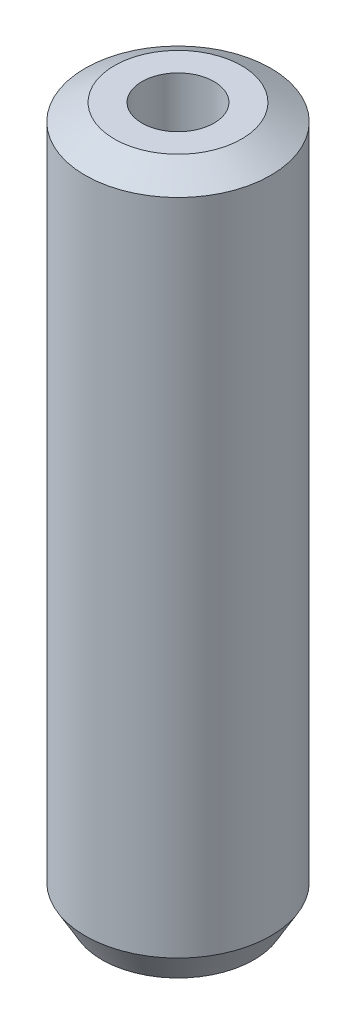
SolidWorks part; units mm, degrees
ref_plane "Front Plane" through (0, 0, 0) normal (0, 0, 1) x (1, 0, 0)
ref_plane "Top Plane" through (0, 0, 0) normal (0, 1, 0) x (1, 0, 0)
ref_plane "Right Plane" through (0, 0, 0) normal (1, 0, 0) x (0, 0, -1)
sketch "Sketch1" plane through (0, 0, 0) normal (0, 1, 0) x (1, 0, 0)
  circle A0 centre (0, 0) radius 22.5
  dimension "SHAFT_OD" = 45
extrude "Boss-Extrude1" add sketch "Sketch1" along normal blind 170.8514
sketch "Sketch2" plane through (0, 0, 0) normal (0, 1, 0) x (1, 0, 0)
  circle A0 centre (0, 0) radius 8.7421
  dimension "BORE_D" = 17.4841
extrude "Cut-Extrude1" cut sketch "Sketch2" along normal through all
chamfer "Chamfer1" distance 4.0844 angle 60 2 edges at (0, 170.8514, 22.5) (0, 0, 22.5) first distance on face at (0, 170.8514, 22.5) first distance on face at (0, 0, 8.7421)
